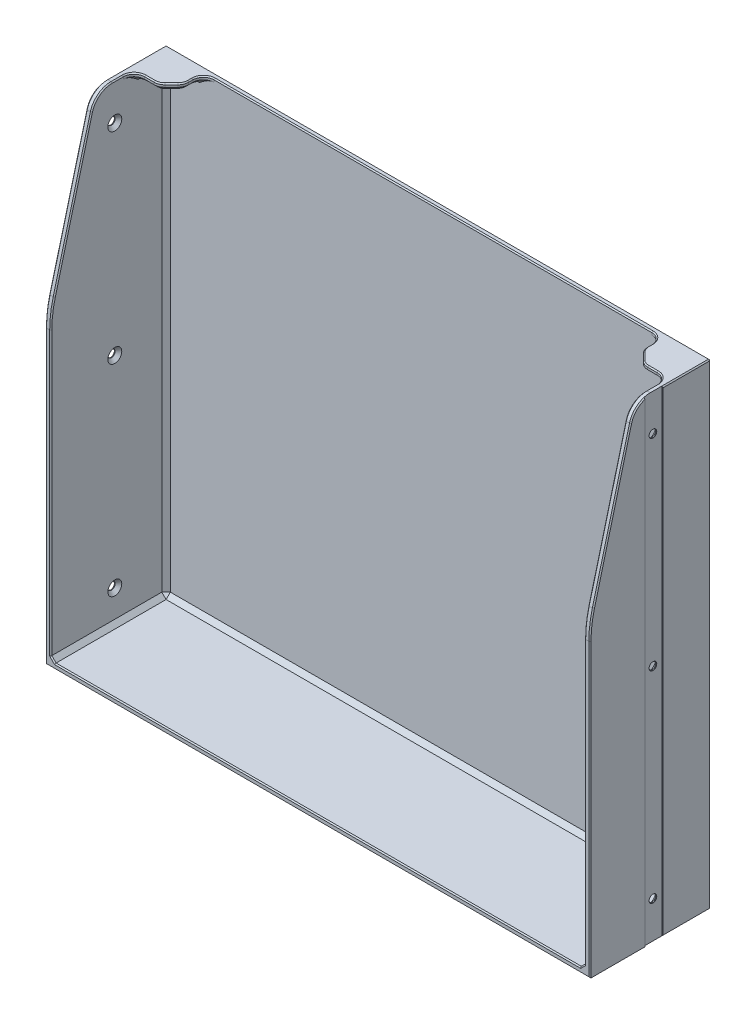
SolidWorks part; units mm, degrees
ref_plane "Front" through (0, 0, 0) normal (0, 0, 1) x (1, 0, 0)
ref_plane "Top" through (0, 0, 0) normal (0, 1, 0) x (1, 0, 0)
ref_plane "Right" through (0, 0, 0) normal (1, 0, 0) x (0, 0, -1)
sketch "Sketch1" plane through (0, 0, 0) normal (0, 0, 1) x (1, 0, 0)
  line L1 (-127.5, -111.5) -> (127.5, -111.5)
  line L2 (-127.5, -111.5) -> (-127.5, 111.5)
  line L3 (-127.5, 111.5) -> (127.5, 111.5)
  line L4 (127.5, -111.5) -> (127.5, 111.5)
  line L5 (-127.5, -111.5) -> (127.5, 111.5) construction
  line L6 (-127.5, 111.5) -> (127.5, -111.5) construction
  point P0 (0, 0)
  dimension "D1" = 223
  dimension "D2" = 255
extrude "Boss-Extrude1" add sketch "Sketch1" against normal blind 2.5
sketch "Sketch2" plane through (0, 0, 0) normal (0, 0, 1) x (1, 0, 0)
  line L0 (-127.5, -111.5) -> (127.5, -111.5) construction
  line L1 (-127.5, 111.5) -> (-125, 111.5)
  line L2 (-127.5, 111.5) -> (-127.5, -111.5)
  line L3 (-127.5, -111.5) -> (-125, -111.5)
  line L4 (-125, 111.5) -> (-125, -111.5)
  line L6 (127.5, 111.5) -> (125, 111.5)
  line L7 (127.5, 111.5) -> (127.5, -111.5)
  line L8 (127.5, -111.5) -> (125, -111.5)
  line L9 (125, 111.5) -> (125, -111.5)
  line L10 (-125, 111.5) -> (125, 111.5)
  line L14 (-125, -111.5) -> (125, -111.5)
  line L15 (-125, -111.5) -> (-125, -109)
  line L16 (-125, -109) -> (125, -109)
  line L17 (125, -111.5) -> (125, -109)
  dimension "D1" = 2.5
extrude "Boss-Extrude2" add sketch "Sketch2" along normal blind 54 contours L4 L1 L2 L3 | L16 L4 L14 L9 | L6 L9 L8 L7
sketch "Sketch5" plane through (0, 0, 0) normal (1, 0, 0) x (0, 0, -1)
  line L0 (-54, 31.5) -> (-33, 111.5)
  line L1 (-54, 111.5) -> (-54, -111.5) construction
  line L2 (2.5, 111.5) -> (-54, 111.5) construction
  line L3 (-33, 111.5) -> (-54, 111.5)
  line L4 (-54, 111.5) -> (-54, 31.5)
  dimension "D1" = 33
  dimension "D2" = 80
extrude "Front Taper" cut sketch "Sketch5" against normal through all both and the other way through all
sketch "Sketch10" plane through (0, 111.5, 0) normal (0, 1, 0) x (1, 0, 0)
  line L0 (127.5, -15) -> (113.5, -15)
  line L1 (127.5, 2.5) -> (127.5, -33) construction
  line L2 (113.5, -15) -> (107.5, -9)
  line L3 (107.5, -9) -> (107.5, 2.5)
  line L4 (127.5, 2.5) -> (-127.5, 2.5) construction
  line L5 (107.5, 2.5) -> (127.5, 2.5)
  line L6 (127.5, 2.5) -> (127.5, -15)
  line L7 (125, 0) -> (-125, 0) construction
  dimension "D1" = 45
  dimension "D2" = 15
  dimension "D3" = 20
  dimension "D4" = 6
extrude "Hold In Tab" add sketch "Sketch10" against normal blind 3
mirror "Hold Tabs" about plane through (0, 0, 0) normal (1, 0, 0) of "Hold In Tab"
sketch "Sketch6" plane through (127, 0, 0) normal (-1, 0, 0) x (0, 0, 1)
  line L4 (19.8, 114.95) -> (19.8, -112.25)
  line L5 (19.8, -112.25) -> (28.2, -112.25)
  line L6 (28.2, -112.25) -> (28.2, 114.95)
  line L7 (28.2, 114.95) -> (19.8, 114.95)
  line L8 (19.8, 114.95) -> (19.8, -112.25)
  line L9 (19.8, -112.25) -> (28.2, -112.25)
  line L10 (28.2, -112.25) -> (28.2, 114.95)
  line L11 (28.2, 114.95) -> (19.8, 114.95)
  dimension "D1" = 0
extrude "Mounting Pocket" cut sketch "Sketch6" against normal through all
mirror "Mounting Pockets" about plane through (0, 0, 0) normal (1, 0, 0) of "Mounting Pocket"
sketch "Sketch7" plane through (125, 0, 0) normal (-1, 0, 0) x (0, 0, 1)
  point P0 (24, -94.2857)
  point P1 (24, 0)
  point P3 (24, 94.2857)
sketch "Sketch8" plane through (125, 0, 0) normal (-1, 0, 0) x (0, 0, 1)
  point P0 (24, -94.2857)
  point P3 (24, 0)
  point P6 (24, 94.2857)
hole_wizard "CSK for M3 Flat Head Machine Screw1" positions "Sketch8" profile "Sketch9" countersink size "M3" standard "ANSI Metric" end condition up to next
sketch "Sketch9" plane through (125, -94.2857, 24) normal (0, 1, 0) x (0, 0, 1)
  line L0 (0, 0) -> (0, 2)
  line L1 (0, 2) -> (1.8, 2)
  line L2 (1.7, 1.9) -> (1.7, 1.55)
  line L3 (1.7, 1.55) -> (3.25, 0)
  line L5 (3.25, 0) -> (0, 0)
  line L6 (-1.7, 1.55) -> (-3.25, 0) construction
  line L7 (1.8, 2) -> (1.7, 1.9)
  line L8 (-1.8, 2) -> (-1.7, 1.9) construction
  line L11 (0, -6.35) -> (0, 107.95) construction
  dimension "Thru Hole Dia." = 3.4
  dimension "Thru Hole Depth" = 2
  dimension "Near C'Sink Dia." = 6.5
  dimension "Near C'Sink Angle" = 90
  dimension "Far C'Sink Dia." = 3.6
  dimension "Far C'Sink Angle" = 90
mirror "Mounting Screw Holes" about plane through (0, 0, 0) normal (1, 0, 0) of "CSK for M3 Flat Head Machine Screw1"
fillet "Fillet2" radius 5 8 edges at (-107.5, 110, 9) (-113.5, 110, 15) (107.5, 110, 9) (113.5, 110, 15) (-125, 110, 15) (-107.5, 110, 0) (107.5, 110, 0) (125, 110, 15)
fillet "Fillet3" radius 10 2 edges at (-126.25, 111.5, 33) (126.25, 111.5, 33)
fillet "Fillet4" radius 50 2 edges at (-126.25, 31.5, 54) (126.25, 31.5, 54)
chamfer "Insert Chams" distance 1.5 angle 45 14 edges at (-117.7855, 108.5, 15) (117.7855, 108.5, 15) (-106.0355, 108.5, 1.4645) (-107.5, 108.5, 5.9645) (-107.8806, 108.5, 8.8423) (-110.5, 108.5, 12) (-113.6577, 108.5, 14.6194) (-123.5355, 108.5, 16.4645) (106.0355, 108.5, 1.4645) (107.5, 108.5, 5.9645) (107.8806, 108.5, 8.8423) (110.5, 108.5, 12) (113.6577, 108.5, 14.6194) (123.5355, 108.5, 16.4645)
chamfer "Inside Chams" distance 2 angle 45 9 edges at (125, 108.5, 7.9233) (-125, 108.5, 7.9233) (-125, -109, 27) (125, -109, 27) (115.8267, 108.5, 0) (-115.8267, 108.5, 0) (-125, -0.25, 0) (0, -109, 0) (125, -0.25, 0)
chamfer "Deburs" distance 0.5 angle 45 49 edges at (127.25, 111.5, 19.8) (127.25, -111.5, 19.8) (-127.5, 0, -2.5) (-127.25, -111.5, 19.8) (-127.25, 111.5, 19.8) (0, -111.5, -2.5) (0, -111.5, 54) (-110.5, 111.5, 12) (-117.7855, 111.5, 15) (-107.5, 111.5, 5.9645) (0, 111.5, 0) (107.5, 111.5, 5.9645) (110.5, 111.5, 12) (117.7855, 111.5, 15) (113.6577, 111.5, 14.6194) (107.8806, 111.5, 8.8423) (-113.6577, 111.5, 14.6194) (-107.8806, 111.5, 8.8423) (-123.5355, 111.5, 16.4645) (-106.0355, 111.5, 1.4645) (106.0355, 111.5, 1.4645) (123.5355, 111.5, 16.4645) (125, 111.5, 22.6431) (-125, 111.5, 22.6431) (-125, 109.418, 31.394) (-127.5, 108.432, 32.4937) (-127.25, 111.0661, 28.2) (127.25, 111.0661, 28.2) (127.5, 108.432, 32.4937) (125, 109.418, 31.394) (-125, 70.8904, 43.66) (-127.5, 70.8904, 43.66) (-125, -40.9766, 54) (-125, 31.4469, 53.5887) (-127.5, -43.2266, 54) (127.5, -43.2266, 54) (125, -40.9766, 54) (-127.5, 31.4469, 53.5887) (127.5, 70.8904, 43.66) (125, 70.8904, 43.66) (127.5, 31.4469, 53.5887) (125, 31.4469, 53.5887) (0, -109, 54) (-124, -108, 54) (124, -108, 54) (127.5, 0, -2.5) (-127.5, 111.5, 8.65) (127.5, 111.5, 8.65) (0, 111.5, -2.5)
